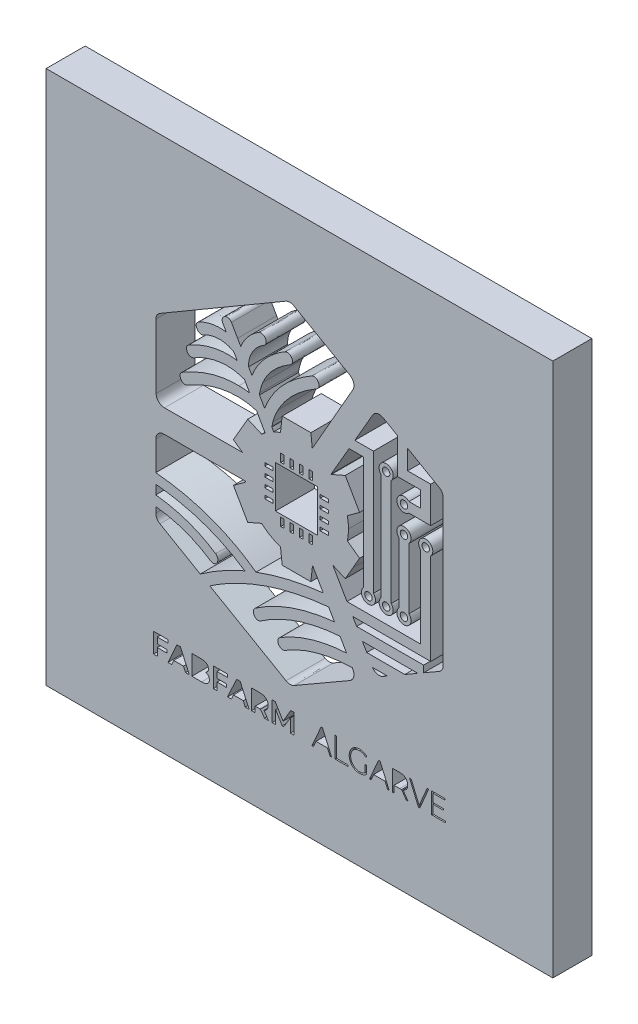
SolidWorks part; units mm, degrees
ref_plane "Front Plane" through (0, 0, 0) normal (0, 0, 1) x (1, 0, 0)
ref_plane "Top Plane" through (0, 0, 0) normal (0, 1, 0) x (1, 0, 0)
ref_plane "Right Plane" through (0, 0, 0) normal (1, 0, 0) x (0, 0, -1)
sketch "Model" plane through (0, 0, 0) normal (0, 0, 1) x (1, 0, 0)
  line L0 (0, 150.5371) -> (142.7565, 150.5371)
  line L1 (142.7565, 150.5371) -> (142.7565, 0)
  line L2 (142.7565, 0) -> (0, 0)
  line L3 (0, 0) -> (0, 150.5371)
  line L4 (31.3066, 27.484) -> (31.3066, 25.7909)
  line L5 (31.3066, 25.7909) -> (33.9926, 25.7909)
  line L6 (33.9926, 25.7909) -> (33.9926, 24.9164)
  line L7 (33.9926, 24.9164) -> (31.3066, 24.9164)
  line L8 (31.3066, 24.9164) -> (31.3066, 22.7852)
  line L9 (31.3066, 22.7852) -> (30.2732, 22.7852)
  line L10 (30.2732, 22.7852) -> (30.2732, 28.35)
  line L11 (30.2732, 28.35) -> (34.336, 28.35)
  line L12 (34.336, 28.35) -> (34.336, 27.484)
  line L13 (34.336, 27.484) -> (31.3066, 27.484)
  line L14 (38.7083, 24.0741) -> (35.9259, 24.0741)
  line L15 (35.9259, 24.0741) -> (35.3779, 22.7869)
  line L16 (35.3779, 22.7869) -> (34.3123, 22.7869)
  line L17 (34.3123, 22.7869) -> (36.8156, 28.3517)
  line L18 (36.8156, 28.3517) -> (37.8339, 28.3517)
  line L19 (37.8339, 28.3517) -> (40.3456, 22.7869)
  line L20 (40.3456, 22.7869) -> (39.2648, 22.7869)
  line L21 (39.2648, 22.7869) -> (38.7083, 24.0741)
  line L22 (38.3667, 24.8843) -> (37.318, 27.3166)
  line L23 (37.318, 27.3166) -> (36.2761, 24.8843)
  line L24 (36.2761, 24.8843) -> (38.3667, 24.8843)
  line L25 (43.8198, 22.7852) -> (41.0543, 22.7852)
  line L26 (41.0543, 22.7852) -> (41.0543, 28.35)
  line L27 (41.0543, 28.35) -> (43.6625, 28.35)
  line L28 (42.0861, 27.5398) -> (42.0861, 26.0057)
  line L29 (42.0861, 26.0057) -> (43.5492, 26.0057)
  line L30 (43.5492, 27.5398) -> (42.0861, 27.5398)
  line L31 (43.7555, 25.2023) -> (42.0861, 25.2023)
  line L32 (42.0861, 25.2023) -> (42.0861, 23.5971)
  line L33 (42.0861, 23.5971) -> (43.7555, 23.5971)
  line L34 (48.1363, 27.484) -> (48.1363, 25.7909)
  line L35 (48.1363, 25.7909) -> (50.824, 25.7909)
  line L36 (50.824, 25.7909) -> (50.824, 24.9164)
  line L37 (50.824, 24.9164) -> (48.1363, 24.9164)
  line L38 (48.1363, 24.9164) -> (48.1363, 22.7852)
  line L39 (48.1363, 22.7852) -> (47.1029, 22.7852)
  line L40 (47.1029, 22.7852) -> (47.1029, 28.35)
  line L41 (47.1029, 28.35) -> (51.1657, 28.35)
  line L42 (51.1657, 28.35) -> (51.1657, 27.484)
  line L43 (51.1657, 27.484) -> (48.1363, 27.484)
  line L44 (55.538, 24.0741) -> (52.7556, 24.0741)
  line L45 (52.7556, 24.0741) -> (52.2076, 22.7869)
  line L46 (52.2076, 22.7869) -> (51.142, 22.7869)
  line L47 (51.142, 22.7869) -> (53.6453, 28.3517)
  line L48 (53.6453, 28.3517) -> (54.6636, 28.3517)
  line L49 (54.6636, 28.3517) -> (57.1753, 22.7869)
  line L50 (57.1753, 22.7869) -> (56.0945, 22.7869)
  line L51 (56.0945, 22.7869) -> (55.538, 24.0741)
  line L52 (55.1947, 24.8843) -> (54.146, 27.3166)
  line L53 (54.146, 27.3166) -> (53.1041, 24.8843)
  line L54 (53.1041, 24.8843) -> (55.1947, 24.8843)
  line L55 (61.524, 22.7852) -> (60.3874, 24.4141)
  line L56 (60.1725, 24.4056) -> (58.9158, 24.4056)
  line L57 (58.9158, 24.4056) -> (58.9158, 22.7835)
  line L58 (58.9158, 22.7835) -> (57.8824, 22.7835)
  line L59 (57.8824, 22.7835) -> (57.8824, 28.3483)
  line L60 (57.8824, 28.3483) -> (60.1725, 28.3483)
  line L61 (61.3582, 24.612) -> (62.6387, 22.7835)
  line L62 (62.6387, 22.7835) -> (61.524, 22.7835)
  line L63 (61.524, 22.7835) -> (61.524, 22.7852)
  line L64 (60.1235, 27.4756) -> (58.9158, 27.4756)
  line L65 (58.9158, 27.4756) -> (58.9158, 25.2581)
  line L66 (58.9158, 25.2581) -> (60.1235, 25.2581)
  line L67 (68.8056, 22.7852) -> (68.7971, 26.4742)
  line L68 (68.7971, 26.4742) -> (66.9687, 23.4212)
  line L69 (66.9687, 23.4212) -> (66.5069, 23.4212)
  line L70 (66.5069, 23.4212) -> (64.6785, 26.4252)
  line L71 (64.6785, 26.4252) -> (64.6785, 22.7852)
  line L72 (64.6785, 22.7852) -> (63.6924, 22.7852)
  line L73 (63.6924, 22.7852) -> (63.6924, 28.35)
  line L74 (63.6924, 28.35) -> (64.5432, 28.35)
  line L75 (64.5432, 28.35) -> (66.7539, 24.661)
  line L76 (66.7539, 24.661) -> (68.924, 28.35)
  line L77 (68.924, 28.35) -> (69.7748, 28.35)
  line L78 (69.7748, 28.35) -> (69.7832, 22.7852)
  line L79 (69.7832, 22.7852) -> (68.8056, 22.7852)
  line L80 (79.2688, 24.3921) -> (76.0415, 24.3921)
  line L81 (76.0415, 24.3921) -> (75.3345, 22.748)
  line L82 (75.3345, 22.748) -> (74.8981, 22.748)
  line L83 (74.8981, 22.748) -> (77.4573, 28.5902)
  line L84 (77.4573, 28.5902) -> (77.8632, 28.5902)
  line L85 (77.8632, 28.5902) -> (80.4223, 22.748)
  line L86 (80.4223, 22.748) -> (79.9859, 22.748)
  line L87 (79.9859, 22.748) -> (79.2688, 24.3921)
  line L88 (79.1182, 24.7507) -> (77.6551, 28.1234)
  line L89 (77.6551, 28.1234) -> (76.2005, 24.7507)
  line L90 (76.2005, 24.7507) -> (79.1182, 24.7507)
  line L91 (81.4084, 28.5902) -> (81.8144, 28.5902)
  line L92 (81.8144, 28.5902) -> (81.8144, 23.132)
  line L93 (81.8144, 23.132) -> (85.0179, 23.132)
  line L94 (85.0179, 23.132) -> (85.0179, 22.748)
  line L95 (85.0179, 22.748) -> (81.4084, 22.748)
  line L96 (81.4084, 22.748) -> (81.4084, 28.5902)
  line L97 (89.8977, 25.6437) -> (90.2867, 25.6437)
  line L98 (90.2867, 25.6437) -> (90.2867, 23.4567)
  line L99 (90.3104, 27.8308) -> (90.0567, 27.5466)
  line L100 (89.8977, 23.6326) -> (89.8977, 25.6437)
  line L101 (95.4862, 24.3921) -> (92.2589, 24.3921)
  line L102 (92.2589, 24.3921) -> (91.5519, 22.748)
  line L103 (91.5519, 22.748) -> (91.1155, 22.748)
  line L104 (91.1155, 22.748) -> (93.6747, 28.5902)
  line L105 (93.6747, 28.5902) -> (94.0806, 28.5902)
  line L106 (94.0806, 28.5902) -> (96.6397, 22.748)
  line L107 (96.6397, 22.748) -> (96.2033, 22.748)
  line L108 (96.2033, 22.748) -> (95.4862, 24.3921)
  line L109 (95.3356, 24.7507) -> (93.8726, 28.1234)
  line L110 (93.8726, 28.1234) -> (92.4179, 24.7507)
  line L111 (92.4179, 24.7507) -> (95.3356, 24.7507)
  line L112 (101.4891, 22.748) -> (100.1613, 24.7016)
  line L113 (99.62, 24.6593) -> (98.0301, 24.6593)
  line L114 (98.0301, 24.6593) -> (98.0301, 22.748)
  line L115 (98.0301, 22.748) -> (97.6241, 22.748)
  line L116 (97.6241, 22.748) -> (97.6241, 28.5902)
  line L117 (97.6241, 28.5902) -> (99.62, 28.5902)
  line L118 (100.5571, 24.7913) -> (101.9474, 22.7463)
  line L119 (101.9474, 22.7463) -> (101.4891, 22.7463)
  line L120 (101.4891, 22.7463) -> (101.4891, 22.748)
  line L121 (99.62, 28.2079) -> (98.0301, 28.2079)
  line L122 (98.0301, 28.2079) -> (98.0301, 25.0365)
  line L123 (98.0301, 25.0365) -> (99.62, 25.0365)
  line L124 (99.62, 25.0365) -> (99.62, 25.0348)
  line L125 (107.7693, 28.5902) -> (105.2897, 22.748)
  line L126 (105.2897, 22.748) -> (104.8838, 22.748)
  line L127 (104.8838, 22.748) -> (102.4041, 28.5902)
  line L128 (102.4041, 28.5902) -> (102.849, 28.5902)
  line L129 (102.849, 28.5902) -> (105.0986, 23.2977)
  line L130 (105.0986, 23.2977) -> (107.3482, 28.5902)
  line L131 (107.3482, 28.5902) -> (107.7693, 28.5902)
  line L132 (112.4833, 23.132) -> (112.4833, 22.748)
  line L133 (112.4833, 22.748) -> (108.6438, 22.748)
  line L134 (108.6438, 22.748) -> (108.6438, 28.5902)
  line L135 (108.6438, 28.5902) -> (112.3649, 28.5902)
  line L136 (112.3649, 28.5902) -> (112.3649, 28.2063)
  line L137 (112.3649, 28.2063) -> (109.0497, 28.2063)
  line L138 (109.0497, 28.2063) -> (109.0497, 25.9025)
  line L139 (109.0497, 25.9025) -> (112.0148, 25.9025)
  line L140 (112.0148, 25.9025) -> (112.0148, 25.527)
  line L141 (112.0148, 25.527) -> (109.0497, 25.527)
  line L142 (109.0497, 25.527) -> (109.0497, 23.132)
  line L143 (109.0497, 23.132) -> (112.4833, 23.132)
  line L144 (33.3296, 84.4124) -> (55.2962, 84.5291)
  line L145 (55.2962, 84.5291) -> (52.7641, 86.3778)
  line L146 (52.7641, 86.3778) -> (56.8049, 93.3871)
  line L147 (56.8049, 93.3871) -> (60.7189, 91.6669)
  line L148 (66.0232, 94.7318) -> (66.4968, 98.9773)
  line L149 (66.4968, 98.9773) -> (74.5784, 98.9773)
  line L150 (74.5784, 98.9773) -> (74.9844, 95.3407)
  line L151 (74.9844, 95.3407) -> (86.4184, 115.374)
  line L152 (85.5507, 118.5471) -> (69.8188, 127.5269)
  line L153 (67.4931, 127.5151) -> (32.0543, 106.8171)
  line L154 (30.9007, 104.7975) -> (30.9903, 86.728)
  line L155 (78.0679, 61.617) -> (75.052, 66.8385)
  line L156 (75.052, 66.8385) -> (74.5801, 62.6082)
  line L157 (74.5801, 62.6082) -> (66.4985, 62.6082)
  line L158 (66.4985, 62.6082) -> (66.0249, 66.8537)
  line L159 (60.7206, 69.9152) -> (56.8066, 68.195)
  line L160 (56.8066, 68.195) -> (52.7658, 75.2043)
  line L161 (52.7658, 75.2043) -> (56.2231, 77.7296)
  line L162 (56.1859, 77.9309) -> (33.2146, 77.9309)
  line L163 (30.8889, 75.6051) -> (30.8889, 67.3662)
  line L164 (84.6509, 50.2202) -> (82.8089, 53.4068)
  line L165 (81.2494, 56.1047) -> (79.6071, 58.9463)
  line L166 (46.1083, 47.3549) -> (67.5878, 34.9534)
  line L167 (69.9135, 34.9534) -> (85.5626, 43.9873)
  line L168 (86.4134, 47.1655) -> (86.2527, 47.4513)
  line L169 (30.8872, 64.5432) -> (30.8872, 61.9469)
  line L170 (30.8855, 59.1154) -> (30.8855, 57.4899)
  line L171 (32.0492, 55.4755) -> (43.4223, 48.9093)
  line L172 (66.101, 89.7387) -> (67.0059, 89.7387)
  line L173 (67.0059, 89.7387) -> (67.0059, 87.479)
  line L174 (67.0059, 87.479) -> (66.101, 87.479)
  line L175 (66.101, 87.479) -> (66.101, 89.7387)
  line L176 (68.7582, 89.7387) -> (69.6632, 89.7387)
  line L177 (69.6632, 89.7387) -> (69.6632, 87.479)
  line L178 (69.6632, 87.479) -> (68.7582, 87.479)
  line L179 (68.7582, 87.479) -> (68.7582, 89.7387)
  line L180 (71.4155, 89.7387) -> (72.3204, 89.7387)
  line L181 (72.3204, 89.7387) -> (72.3204, 87.479)
  line L182 (72.3204, 87.479) -> (71.4155, 87.479)
  line L183 (71.4155, 87.479) -> (71.4155, 89.7387)
  line L184 (74.0727, 89.7387) -> (74.9776, 89.7387)
  line L185 (74.9776, 89.7387) -> (74.9776, 87.479)
  line L186 (74.9776, 87.479) -> (74.0727, 87.479)
  line L187 (74.0727, 87.479) -> (74.0727, 89.7387)
  line L188 (66.101, 74.1048) -> (67.0059, 74.1048)
  line L189 (67.0059, 74.1048) -> (67.0059, 71.8451)
  line L190 (67.0059, 71.8451) -> (66.101, 71.8451)
  line L191 (66.101, 71.8451) -> (66.101, 74.1048)
  line L192 (68.7582, 74.1048) -> (69.6632, 74.1048)
  line L193 (69.6632, 74.1048) -> (69.6632, 71.8451)
  line L194 (69.6632, 71.8451) -> (68.7582, 71.8451)
  line L195 (68.7582, 71.8451) -> (68.7582, 74.1048)
  line L196 (71.4155, 74.1048) -> (72.3204, 74.1048)
  line L197 (72.3204, 74.1048) -> (72.3204, 71.8451)
  line L198 (72.3204, 71.8451) -> (71.4155, 71.8451)
  line L199 (71.4155, 71.8451) -> (71.4155, 74.1048)
  line L200 (74.0727, 74.1048) -> (74.9776, 74.1048)
  line L201 (74.9776, 74.1048) -> (74.9776, 71.8451)
  line L202 (74.9776, 71.8451) -> (74.0727, 71.8451)
  line L203 (74.0727, 71.8451) -> (74.0727, 74.1048)
  line L204 (61.5933, 77.2577) -> (63.8531, 77.2577)
  line L205 (63.8531, 77.2577) -> (63.8531, 76.3528)
  line L206 (63.8531, 76.3528) -> (61.5933, 76.3528)
  line L207 (61.5933, 76.3528) -> (61.5933, 77.2577)
  line L208 (61.5933, 79.9149) -> (63.8531, 79.9149)
  line L209 (63.8531, 79.9149) -> (63.8531, 79.01)
  line L210 (63.8531, 79.01) -> (61.5933, 79.01)
  line L211 (61.5933, 79.01) -> (61.5933, 79.9149)
  line L212 (61.5933, 82.5721) -> (63.8531, 82.5721)
  line L213 (63.8531, 82.5721) -> (63.8531, 81.6672)
  line L214 (63.8531, 81.6672) -> (61.5933, 81.6672)
  line L215 (61.5933, 81.6672) -> (61.5933, 82.5721)
  line L216 (61.5933, 85.2294) -> (63.8531, 85.2294)
  line L217 (63.8531, 85.2294) -> (63.8531, 84.3245)
  line L218 (63.8531, 84.3245) -> (61.5933, 84.3245)
  line L219 (61.5933, 84.3245) -> (61.5933, 85.2294)
  line L220 (77.2255, 77.2577) -> (79.4853, 77.2577)
  line L221 (79.4853, 77.2577) -> (79.4853, 76.3528)
  line L222 (79.4853, 76.3528) -> (77.2255, 76.3528)
  line L223 (77.2255, 76.3528) -> (77.2255, 77.2577)
  line L224 (77.2255, 79.9149) -> (79.4853, 79.9149)
  line L225 (79.4853, 79.9149) -> (79.4853, 79.01)
  line L226 (79.4853, 79.01) -> (77.2255, 79.01)
  line L227 (77.2255, 79.01) -> (77.2255, 79.9149)
  line L228 (77.2255, 85.2294) -> (79.4853, 85.2294)
  line L229 (79.4853, 85.2294) -> (79.4853, 84.3245)
  line L230 (79.4853, 84.3245) -> (77.2255, 84.3245)
  line L231 (77.2255, 84.3245) -> (77.2255, 85.2294)
  line L232 (94.9111, 49.6637) -> (96.1655, 50.388)
  line L235 (110.775, 103.6592) -> (101.8453, 108.8143)
  line L244 (99.0253, 110.4441) -> (94.9821, 112.7793)
  line L245 (91.9883, 111.9776) -> (86.9734, 103.2974)
  line L250 (85.3423, 100.4774) -> (80.287, 91.7295)
  line L251 (80.3597, 91.6686) -> (84.2737, 93.3888)
  line L252 (84.2737, 93.3888) -> (88.3145, 86.3795)
  line L253 (88.3145, 86.3795) -> (84.8572, 83.8542)
  line L254 (84.8572, 77.7313) -> (88.3145, 75.206)
  line L255 (88.3145, 75.206) -> (86.4658, 71.999)
  line L256 (86.4658, 71.999) -> (84.2737, 68.1967)
  line L257 (84.2737, 68.1967) -> (80.7894, 69.7274)
  line L258 (80.7894, 69.7274) -> (84.7572, 62.8604)
  line L263 (86.385, 60.0404) -> (87.4799, 58.1459)
  line L266 (106.3516, 56.2707) -> (110.775, 58.8245)
  line L267 (111.871, 60.7223) -> (111.871, 101.7614)
  line L272 (64.6092, 86.7212) -> (76.4678, 86.7212)
  line L273 (76.4678, 86.7212) -> (76.4678, 74.8626)
  line L274 (76.4678, 74.8626) -> (64.6092, 74.8626)
  line L275 (64.6092, 74.8626) -> (64.6092, 86.7212)
  line L277 (104.4666, 55.3259) -> (104.4666, 55.1822)
  line L278 (89.1092, 55.3259) -> (90.3327, 53.208)
  line L279 (104.4666, 55.1822) -> (101.0485, 53.208)
  line L281 (92.2177, 68.5856) -> (92.2177, 103.2974)
  line L282 (77.2255, 82.5721) -> (79.4853, 82.5721)
  line L283 (77.2255, 82.5721) -> (77.2255, 81.6672)
  line L284 (77.2255, 81.6672) -> (79.4853, 81.6672)
  line L285 (79.4853, 82.5721) -> (79.4853, 81.6672)
  line L286 (92.2177, 103.2974) -> (86.9734, 103.2974)
  line L287 (97.2091, 68.6018) -> (97.2074, 98.6357)
  line L288 (102.2225, 68.5917) -> (102.2225, 85.7859)
  line L289 (108.3572, 60.0404) -> (86.385, 60.0404)
  line L290 (108.3572, 60.0404) -> (108.3603, 85.7855)
  line L291 (99.0253, 110.4441) -> (99.0253, 100.4774)
  line L292 (99.0253, 100.4774) -> (105.5407, 100.4774)
  line L293 (105.5407, 100.4774) -> (105.5407, 95.9913)
  line L295 (105.5407, 95.9913) -> (102.2189, 95.9913)
  line L296 (106.3516, 56.2707) -> (106.3516, 58.1459)
  line L297 (106.3516, 58.1459) -> (87.4799, 58.1459)
  line L305 (91.9641, 50.388) -> (96.1655, 50.388)
  line L306 (89.3977, 68.5925) -> (89.3977, 100.4774)
  line L312 (94.3891, 68.5819) -> (94.3874, 98.6385)
  line L315 (99.4025, 68.5925) -> (99.4025, 85.7854)
  line L318 (105.5375, 62.8604) -> (84.7572, 62.8604)
  line L319 (105.5375, 62.8604) -> (105.5403, 85.7858)
  line L320 (101.8453, 108.8143) -> (101.8453, 103.2974)
  line L321 (101.8453, 103.2974) -> (108.3607, 103.2974)
  line L322 (108.3607, 103.2974) -> (108.3607, 93.1713)
  line L323 (108.3607, 93.1713) -> (102.2155, 93.1713)
  line L325 (104.4666, 55.3259) -> (89.1092, 55.3259)
  line L326 (90.3327, 53.208) -> (101.0485, 53.208)
  line L329 (89.3977, 100.4774) -> (85.3423, 100.4774)
  arc A0 (102.2189, 95.9913) -> (102.2155, 93.1713) centre (100.8142, 94.583) ccw
  circle A1 centre (100.8142, 94.583) radius 1.0453
  circle A2 centre (100.8142, 67.1903) radius 1.0453
  circle A3 centre (100.8125, 87.1863) radius 1.0453
  arc A4 (102.2225, 85.7785) -> (99.4025, 85.7785) centre (100.8125, 87.1863) ccw
  arc A5 (99.4025, 68.594) -> (102.2225, 68.5974) centre (100.8142, 67.1903) ccw
  circle A6 centre (90.8043, 67.1903) radius 1.0453
  arc A7 (89.3977, 68.5925) -> (92.2177, 68.5856) centre (90.8043, 67.1903) ccw
  circle A8 centre (95.8092, 67.1886) radius 1.0453
  arc A9 (94.3891, 68.5819) -> (97.2091, 68.6022) centre (95.8092, 67.1886) ccw
  circle A10 centre (95.7974, 100.0378) radius 1.0453
  arc A11 (97.2074, 98.63) -> (94.3874, 98.63) centre (95.7974, 100.0378) ccw
  circle A12 centre (106.9473, 87.1863) radius 1.0453
  arc A13 (108.3603, 85.7815) -> (105.5403, 85.7755) centre (106.9473, 87.1863) ccw
  spline S0 degree 3 poles (45.9984, 24.2957) (45.9984, 23.3417) (45.2508, 22.7852) (43.8198, 22.7852) knots 0 0 0 0 1 1 1 1
  spline S1 degree 3 poles (43.6625, 28.35) (44.9987, 28.35) (45.7142, 27.7851) (45.7142, 26.9039) knots 0 0 0 0 1 1 1 1
  spline S2 degree 3 poles (45.7142, 26.9039) (45.7142, 26.3322) (45.4284, 25.9093) (44.9987, 25.6793) knots 0 0 0 0 1 1 1 1
  spline S3 degree 3 poles (44.9987, 25.6793) (45.5924, 25.4881) (45.9984, 25.0196) (45.9984, 24.2957) knots 0 0 0 0 1 1 1 1
  spline S4 degree 3 poles (43.5492, 26.0057) (44.2647, 26.0057) (44.6706, 26.2594) (44.6706, 26.7685) knots 0 0 0 0 1 1 1 1
  spline S5 degree 3 poles (44.6706, 26.7685) (44.6706, 27.2844) (44.2647, 27.5398) (43.5492, 27.5398) knots 0 0 0 0 1 1 1 1
  spline S6 degree 3 poles (44.9565, 24.3988) (44.9565, 24.9553) (44.5353, 25.2023) (43.7555, 25.2023) knots 0 0 0 0 1 1 1 1
  spline S7 degree 3 poles (43.7555, 23.5971) (44.5353, 23.5971) (44.9565, 23.8424) (44.9565, 24.3988) knots 0 0 0 0 1 1 1 1
  spline S8 degree 3 poles (60.3874, 24.4141) (60.3163, 24.4056) (60.2436, 24.4056) (60.1725, 24.4056) knots 0 0 0 0 1 1 1 1
  spline S9 degree 3 poles (60.1725, 28.3483) (61.6356, 28.3483) (62.5422, 27.6007) (62.5422, 26.3694) knots 0 0 0 0 1 1 1 1
  spline S10 degree 3 poles (62.5422, 26.3694) (62.5422, 25.527) (62.1126, 24.9063) (61.3582, 24.612) knots 0 0 0 0 1 1 1 1
  spline S11 degree 3 poles (60.1235, 25.2581) (61.0301, 25.2581) (61.4986, 25.6708) (61.4986, 26.3711) knots 0 0 0 0 1 1 1 1
  spline S12 degree 3 poles (61.4986, 26.3711) (61.4986, 27.0713) (61.0301, 27.4756) (60.1235, 27.4756) knots 0 0 0 0 1 1 1 1
  spline S13 degree 3 poles (90.2867, 23.4567) (89.7861, 22.9561) (89.0621, 22.7057) (88.2993, 22.7057) knots 0 0 0 0 1 1 1 1
  spline S14 degree 3 poles (88.2993, 22.7057) (86.6214, 22.7057) (85.39, 23.9658) (85.39, 25.6691) knots 0 0 0 0 1 1 1 1
  spline S15 degree 3 poles (85.39, 25.6691) (85.39, 27.3724) (86.6214, 28.6325) (88.3078, 28.6325) knots 0 0 0 0 1 1 1 1
  spline S16 degree 3 poles (88.3078, 28.6325) (89.1112, 28.6325) (89.8182, 28.3652) (90.3104, 27.8308) knots 0 0 0 0 1 1 1 1
  spline S17 degree 3 poles (90.0567, 27.5466) (89.5713, 28.0473) (88.9911, 28.2401) (88.3162, 28.2401) knots 0 0 0 0 1 1 1 1
  spline S18 degree 3 poles (88.3162, 28.2401) (86.87, 28.2401) (85.796, 27.139) (85.796, 25.6691) knots 0 0 0 0 1 1 1 1
  spline S19 degree 3 poles (85.796, 25.6691) (85.796, 24.2077) (86.8684, 23.0981) (88.3162, 23.0981) knots 0 0 0 0 1 1 1 1
  spline S20 degree 3 poles (88.3162, 23.0981) (88.9048, 23.0981) (89.4444, 23.2487) (89.8977, 23.6326) knots 0 0 0 0 1 1 1 1
  spline S21 degree 3 poles (100.1613, 24.7016) (99.9871, 24.6762) (99.8112, 24.6593) (99.62, 24.6593) knots 0 0 0 0 1 1 1 1
  spline S22 degree 3 poles (99.62, 28.5902) (101.0188, 28.5902) (101.8612, 27.8561) (101.8612, 26.6197) knots 0 0 0 0 1 1 1 1
  spline S23 degree 3 poles (101.8612, 26.6197) (101.8612, 25.6928) (101.3842, 25.05) (100.5571, 24.7913) knots 0 0 0 0 1 1 1 1
  spline S24 degree 3 poles (99.62, 25.0348) (100.8125, 25.0348) (101.4485, 25.6184) (101.4485, 26.6214) knots 0 0 0 0 1 1 1 1
  spline S25 degree 3 poles (101.4485, 26.6214) (101.4485, 27.6312) (100.8125, 28.2079) (99.62, 28.2079) knots 0 0 0 0 1 1 1 1
  spline S26 degree 3 poles (60.7189, 91.6669) (61.0318, 91.9494) (61.3599, 92.215) (61.6982, 92.4704) knots 0 0 0 0 1 1 1 1
  spline S27 degree 3 poles (61.6982, 92.4704) (61.1299, 93.4632) (60.5599, 94.4578) (59.9916, 95.4507) knots 0 0 0 0 1 1 1 1
  spline S28 degree 3 poles (59.9916, 95.4507) (59.7666, 95.8448) (59.5416, 96.2372) (59.315, 96.6313) knots 0 0 0 0 1 1 1 1
  spline S29 degree 3 poles (59.315, 96.6313) (58.948, 96.748) (58.5843, 96.8698) (58.2105, 96.9662) knots 0 0 0 0 1 1 1 1
  spline S30 degree 3 poles (58.2105, 96.9662) (56.9318, 97.296) (55.6243, 97.4465) (54.305, 97.4736) knots 0 0 0 0 1 1 1 1
  spline S31 degree 3 poles (54.305, 97.4736) (49.1546, 97.5802) (44.2308, 95.772) (39.8382, 93.196) knots 0 0 0 0 1 1 1 1
  spline S32 degree 3 poles (39.8382, 93.196) (38.2669, 92.2742) (36.8494, 94.7149) (38.414, 95.6316) knots 0 0 0 0 1 1 1 1
  spline S33 degree 3 poles (38.414, 95.6316) (43.2177, 98.4479) (48.6742, 100.4133) (54.305, 100.2949) knots 0 0 0 0 1 1 1 1
  spline S34 degree 3 poles (54.305, 100.2949) (55.3097, 100.2729) (56.3448, 100.1951) (57.3665, 100.0344) knots 0 0 0 0 1 1 1 1
  spline S35 degree 3 poles (57.3665, 100.0344) (56.8743, 100.8937) (56.3838, 101.7512) (55.8915, 102.6105) knots 0 0 0 0 1 1 1 1
  spline S36 degree 3 poles (55.8915, 102.6105) (55.8036, 102.6426) (55.6953, 102.6764) (55.4636, 102.7576) knots 0 0 0 0 1 1 1 1
  spline S37 degree 3 poles (55.4636, 102.7576) (54.4927, 103.0993) (53.4762, 103.3344) (52.4529, 103.4393) knots 0 0 0 0 1 1 1 1
  spline S38 degree 3 poles (52.4529, 103.4393) (48.6218, 103.8368) (44.9311, 102.6815) (41.643, 100.7702) knots 0 0 0 0 1 1 1 1
  spline S39 degree 3 poles (41.643, 100.7702) (40.0682, 99.8551) (38.6491, 102.2942) (40.2188, 103.2059) knots 0 0 0 0 1 1 1 1
  spline S40 degree 3 poles (40.2188, 103.2059) (44.1023, 105.4622) (49.2206, 106.9777) (53.8534, 106.1709) knots 0 0 0 0 1 1 1 1
  spline S41 degree 3 poles (53.8534, 106.1709) (53.5405, 106.7173) (53.2292, 107.2619) (52.9163, 107.8082) knots 0 0 0 0 1 1 1 1
  spline S42 degree 3 poles (52.9163, 107.8082) (50.3166, 109.4202) (46.9997, 109.1935) (44.3932, 107.7203) knots 0 0 0 0 1 1 1 1
  spline S43 degree 3 poles (44.3932, 107.7203) (42.8084, 106.8255) (41.3892, 109.2629) (42.969, 110.1559) knots 0 0 0 0 1 1 1 1
  spline S44 degree 3 poles (42.969, 110.1559) (45.2829, 111.4634) (48.1042, 112.0317) (50.7479, 111.5953) knots 0 0 0 0 1 1 1 1
  spline S45 degree 3 poles (50.7479, 111.5953) (50.4265, 112.1569) (50.1035, 112.7201) (49.7821, 113.2817) knots 0 0 0 0 1 1 1 1
  spline S46 degree 3 poles (49.7821, 113.2817) (48.8772, 114.8615) (51.3162, 116.2806) (52.2178, 114.7059) knots 0 0 0 0 1 1 1 1
  spline S47 degree 3 poles (52.2178, 114.7059) (52.7912, 113.7029) (53.3662, 112.7015) (53.9396, 111.6985) knots 0 0 0 0 1 1 1 1
  spline S48 degree 3 poles (53.9396, 111.6985) (54.2424, 111.1708) (54.5435, 110.6431) (54.8462, 110.1153) knots 0 0 0 0 1 1 1 1
  spline S49 degree 3 poles (54.8462, 110.1153) (55.7782, 112.595) (57.6472, 114.7431) (59.8918, 116.0844) knots 0 0 0 0 1 1 1 1
  spline S50 degree 3 poles (59.8918, 116.0844) (61.4563, 117.0181) (62.8721, 114.579) (61.316, 113.6487) knots 0 0 0 0 1 1 1 1
  spline S51 degree 3 poles (61.316, 113.6487) (58.7484, 112.1146) (56.9267, 109.3204) (57.0468, 106.2741) knots 0 0 0 0 1 1 1 1
  spline S52 degree 3 poles (57.0468, 106.2741) (57.3479, 105.7481) (57.6489, 105.222) (57.95, 104.696) knots 0 0 0 0 1 1 1 1
  spline S53 degree 3 poles (57.95, 104.696) (57.9686, 104.6825) (57.9923, 104.6689) (58.0092, 104.6554) knots 0 0 0 0 1 1 1 1
  spline S54 degree 3 poles (58.0092, 104.6554) (59.5839, 109.0836) (63.4319, 112.8064) (67.2952, 115.0662) knots 0 0 0 0 1 1 1 1
  spline S55 degree 3 poles (67.2952, 115.0662) (68.8665, 115.9863) (70.2856, 113.5456) (68.7193, 112.6305) knots 0 0 0 0 1 1 1 1
  spline S56 degree 3 poles (68.7193, 112.6305) (65.4447, 110.7158) (62.5862, 108.045) (61.0707, 104.51) knots 0 0 0 0 1 1 1 1
  spline S57 degree 3 poles (61.0707, 104.51) (60.658, 103.5458) (60.3738, 102.531) (60.1793, 101.5009) knots 0 0 0 0 1 1 1 1
  spline S58 degree 3 poles (60.1793, 101.5009) (60.088, 101.0222) (60.1286, 101.3351) (60.1049, 100.9343) knots 0 0 0 0 1 1 1 1
  spline S59 degree 3 poles (60.1049, 100.9343) (60.592, 100.0852) (61.0775, 99.2344) (61.5646, 98.3853) knots 0 0 0 0 1 1 1 1
  spline S60 degree 3 poles (61.5646, 98.3853) (61.9418, 99.434) (62.4205, 100.4488) (62.9313, 101.3994) knots 0 0 0 0 1 1 1 1
  spline S61 degree 3 poles (62.9313, 101.3994) (65.5885, 106.3468) (69.9794, 110.1272) (74.7797, 112.9147) knots 0 0 0 0 1 1 1 1
  spline S62 degree 3 poles (74.7797, 112.9147) (76.3544, 113.8297) (77.7735, 111.3907) (76.2039, 110.479) knots 0 0 0 0 1 1 1 1
  spline S63 degree 3 poles (76.2039, 110.479) (71.796, 107.9199) (67.8077, 104.515) (65.3669, 99.9752) knots 0 0 0 0 1 1 1 1
  spline S64 degree 3 poles (65.3669, 99.9752) (64.7343, 98.7997) (64.2252, 97.5683) (63.8835, 96.2761) knots 0 0 0 0 1 1 1 1
  spline S65 degree 3 poles (63.8835, 96.2761) (63.7837, 95.9023) (63.7127, 95.5251) (63.6349, 95.1462) knots 0 0 0 0 1 1 1 1
  spline S66 degree 3 poles (63.6349, 95.1462) (63.6315, 95.1276) (63.6281, 95.1141) (63.6248, 95.1005) knots 0 0 0 0 1 1 1 1
  spline S67 degree 3 poles (63.6248, 95.1005) (63.6248, 95.0904) (63.6231, 95.0785) (63.6214, 95.0633) knots 0 0 0 0 1 1 1 1
  spline S68 degree 3 poles (63.6214, 95.0633) (63.6146, 94.9906) (63.5977, 94.9246) (63.5842, 94.8587) knots 0 0 0 0 1 1 1 1
  spline S69 degree 3 poles (63.5842, 94.8587) (63.7567, 94.5559) (63.9292, 94.2548) (64.1034, 93.9521) knots 0 0 0 0 1 1 1 1
  spline S70 degree 3 poles (64.1034, 93.9521) (64.7208, 94.2531) (65.3619, 94.517) (66.0232, 94.7318) knots 0 0 0 0 1 1 1 1
  spline S71 degree 3 poles (86.4184, 115.374) (87.0544, 116.4903) (86.6671, 117.9111) (85.5507, 118.5471) knots 0 0 0 0 1 1 1 1
  spline S72 degree 3 poles (69.8188, 127.5269) (69.0965, 127.9396) (68.2102, 127.9345) (67.4931, 127.5151) knots 0 0 0 0 1 1 1 1
  spline S73 degree 3 poles (32.0543, 106.8171) (31.3371, 106.3976) (30.8973, 105.628) (30.9007, 104.7975) knots 0 0 0 0 1 1 1 1
  spline S74 degree 3 poles (30.9903, 86.728) (30.9971, 85.4425) (32.0441, 84.4056) (33.3296, 84.4124) knots 0 0 0 0 1 1 1 1
  spline S75 degree 3 poles (66.0249, 66.8537) (64.0375, 67.4964) (62.2344, 68.5485) (60.7206, 69.9152) knots 0 0 0 0 1 1 1 1
  spline S76 degree 3 poles (56.2231, 77.7296) (56.2095, 77.7955) (56.1977, 77.8649) (56.1859, 77.9309) knots 0 0 0 0 1 1 1 1
  spline S77 degree 3 poles (33.2146, 77.9309) (31.9291, 77.9309) (30.8889, 76.8889) (30.8889, 75.6051) knots 0 0 0 0 1 1 1 1
  spline S78 degree 3 poles (30.8889, 67.3662) (41.0188, 66.4883) (50.8815, 63.2729) (59.1137, 57.2075) knots 0 0 0 0 1 1 1 1
  spline S79 degree 3 poles (59.1137, 57.2075) (65.1893, 59.4723) (71.5795, 60.9202) (78.0679, 61.617) knots 0 0 0 0 1 1 1 1
  spline S80 degree 3 poles (86.2527, 47.4513) (79.602, 47.3448) (73.0984, 45.7345) (67.373, 42.2502) knots 0 0 0 0 1 1 1 1
  spline S81 degree 3 poles (67.373, 42.2502) (65.8168, 41.303) (64.3994, 43.7437) (65.9488, 44.6858) knots 0 0 0 0 1 1 1 1
  spline S82 degree 3 poles (65.9488, 44.6858) (71.6218, 48.138) (78.0695, 49.8937) (84.6509, 50.2202) knots 0 0 0 0 1 1 1 1
  spline S83 degree 3 poles (82.8089, 53.4068) (74.8338, 52.8825) (67.1091, 50.5145) (60.4635, 45.9798) knots 0 0 0 0 1 1 1 1
  spline S84 degree 3 poles (60.4635, 45.9798) (58.9581, 44.9531) (57.5491, 47.3989) (59.0393, 48.4154) knots 0 0 0 0 1 1 1 1
  spline S85 degree 3 poles (59.0393, 48.4154) (65.6511, 52.9265) (73.3386, 55.3757) (81.2494, 56.1047) knots 0 0 0 0 1 1 1 1
  spline S86 degree 3 poles (79.6071, 58.9463) (67.6504, 57.8705) (56.0421, 54.1122) (46.1083, 47.3549) knots 0 0 0 0 1 1 1 1
  spline S87 degree 3 poles (67.5878, 34.9534) (68.3066, 34.5373) (69.1946, 34.5373) (69.9135, 34.9534) knots 0 0 0 0 1 1 1 1
  spline S88 degree 3 poles (85.5626, 43.9873) (86.6755, 44.63) (87.0561, 46.0525) (86.4134, 47.1655) knots 0 0 0 0 1 1 1 1
  spline S89 degree 3 poles (30.8872, 61.9469) (36.8867, 61.3143) (42.695, 59.4266) (47.7355, 56.0201) knots 0 0 0 0 1 1 1 1
  spline S90 degree 3 poles (47.7355, 56.0201) (49.2341, 55.0086) (47.8201, 52.5645) (46.3113, 53.5844) knots 0 0 0 0 1 1 1 1
  spline S91 degree 3 poles (46.3113, 53.5844) (41.67, 56.7187) (36.3911, 58.4963) (30.8855, 59.1154) knots 0 0 0 0 1 1 1 1
  spline S92 degree 3 poles (30.8855, 57.4899) (30.8855, 56.6595) (31.3286, 55.8915) (32.0492, 55.4755) knots 0 0 0 0 1 1 1 1
  spline S93 degree 3 poles (43.4223, 48.9093) (47.3617, 51.734) (51.5801, 54.075) (55.9913, 55.9626) knots 0 0 0 0 1 1 1 1
  spline S94 degree 3 poles (55.9913, 55.9626) (48.5254, 60.976) (39.85, 63.7584) (30.8872, 64.5432) knots 0 0 0 0 1 1 1 1
  spline S107 degree 3 poles (91.9641, 50.388) (92.5884, 49.4027) (93.8904, 49.075) (94.9111, 49.6637) knots 0.025111 0.025111 0.025111 0.025111 1 1 1 1
  spline S112 degree 3 poles (94.9821, 112.7793) (94.6371, 112.9789) (94.2616, 113.072) (93.8895, 113.072) knots 0 0 0 0 1 1 1 1
  spline S113 degree 3 poles (93.8895, 113.072) (93.1317, 113.072) (92.3943, 112.6795) (91.9883, 111.9776) knots 0 0 0 0 1 1 1 1
  spline S118 degree 3 poles (80.287, 91.7295) (80.3107, 91.7092) (80.3361, 91.6889) (80.3597, 91.6686) knots 0 0 0 0 1 1 1 1
  spline S119 degree 3 poles (84.8572, 83.8542) (85.067, 82.8664) (85.1888, 81.8431) (85.1888, 80.7927) knots 0 0 0 0 1 1 1 1
  spline S120 degree 3 poles (85.1888, 80.7927) (85.1888, 79.7424) (85.067, 78.7191) (84.8572, 77.7313) knots 0 0 0 0 1 1 1 1
  spline S125 degree 3 poles (110.775, 58.8245) (111.4516, 59.2152) (111.871, 59.9425) (111.871, 60.7223) knots 0 0 0 0 1 1 1 1
  spline S126 degree 3 poles (111.871, 101.7614) (111.8694, 102.5411) (111.4499, 103.2684) (110.775, 103.6592) knots 0 0 0 0 1 1 1 1
extrude "Boss-Extrude1" add sketch "Model" against normal blind 11 contours L3 L2 L1 L0 S126 L267 S125 L266 L296 L297 L263 L289 L290 A13 L319 L318 L258 L257 L256 L255 L254 S120 S119 L253 L252 L251 S118 L250 L329 L306 A7 L281 L286 L245 S113 S112 L244 L291 L292 L293 L295 A0 L323 L322 L321 L320 | A11 L312 A9 L287 A8 A10 | A5 L288 A4 L315 A2 A3 region at (71.7329, 74.4432, 0) region at (95.7991, 83.618, 0) region at (100.8127, 77.1909, 0)
